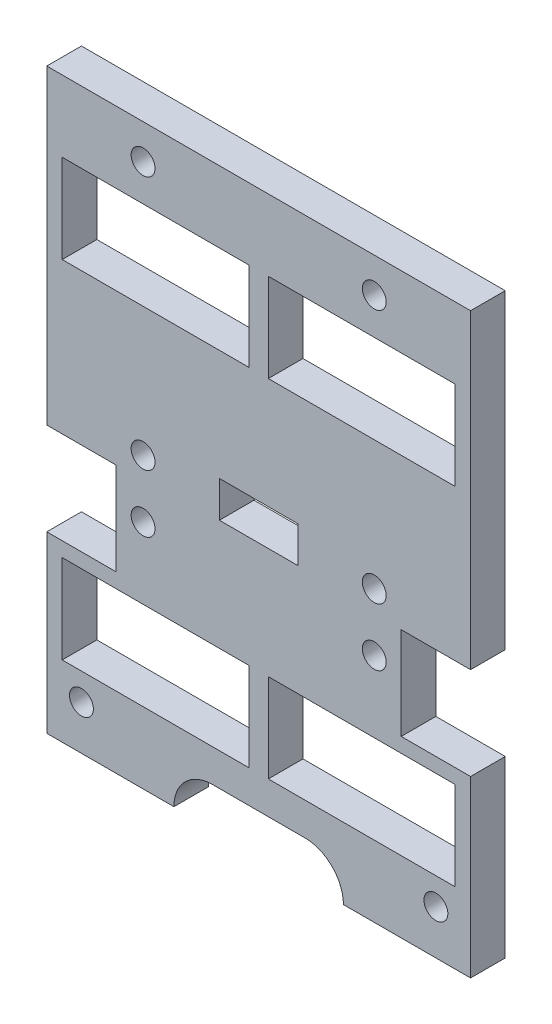
SolidWorks part; units mm, degrees
ref_plane "Front Plane" through (0, 0, 0) normal (0, 0, 1) x (1, 0, 0)
ref_plane "Top Plane" through (0, 0, 0) normal (0, 1, 0) x (1, 0, 0)
ref_plane "Right Plane" through (0, 0, 0) normal (1, 0, 0) x (0, 0, -1)
sketch "Sketch1" plane through (0, 0, 0) normal (0, 0, 1) x (1, 0, 0)
  line L0 (0, -37.5) -> (0, 37.5) construction
  line L1 (-27.5, -37.5) -> (27.5, -37.5)
  line L2 (-27.5, -37.5) -> (-27.5, 37.5)
  line L3 (-27.5, 37.5) -> (27.5, 37.5)
  line L4 (27.5, -37.5) -> (27.5, 37.5)
  line L5 (-27.5, -37.5) -> (27.5, 37.5) construction
  line L6 (-27.5, 37.5) -> (27.5, -37.5) construction
  line L7 (-27.5, 0) -> (27.5, 0) construction
  line L8 (-27.5, 22.5) -> (27.5, 22.5) construction
  line L9 (25.5, 16.75) -> (1.25, 28.25) construction
  line L10 (-25.5, 28.25) -> (-1.25, 28.25)
  line L11 (-25.5, 28.25) -> (-25.5, 16.75)
  line L12 (-25.5, 16.75) -> (-1.25, 16.75)
  line L13 (-1.25, 28.25) -> (-1.25, 16.75)
  line L14 (-25.5, 28.25) -> (-1.25, 16.75) construction
  line L15 (-25.5, 16.75) -> (-1.25, 28.25) construction
  line L16 (25.5, 28.25) -> (1.25, 16.75) construction
  line L17 (1.25, 28.25) -> (1.25, 16.75)
  line L18 (25.5, 16.75) -> (1.25, 16.75)
  line L19 (25.5, 28.25) -> (25.5, 16.75)
  line L20 (25.5, 28.25) -> (1.25, 28.25)
  line L21 (25.5, -28.25) -> (1.25, -16.75) construction
  line L22 (-25.5, -16.75) -> (-1.25, -28.25) construction
  line L23 (-25.5, -28.25) -> (-1.25, -16.75) construction
  line L24 (25.5, -16.75) -> (1.25, -28.25) construction
  line L25 (25.5, -28.25) -> (1.25, -28.25)
  line L26 (25.5, -28.25) -> (25.5, -16.75)
  line L27 (25.5, -16.75) -> (1.25, -16.75)
  line L28 (1.25, -28.25) -> (1.25, -16.75)
  line L29 (-1.25, -28.25) -> (-1.25, -16.75)
  line L30 (-25.5, -16.75) -> (-1.25, -16.75)
  line L31 (-25.5, -28.25) -> (-25.5, -16.75)
  line L32 (-25.5, -28.25) -> (-1.25, -28.25)
  point P0 (0, 0)
  point P12 (-13.375, 22.5)
  point P21 (13.375, 22.5)
  point P30 (13.375, -22.5)
  point P31 (-13.375, -22.5)
  dimension "D1" = 55
  dimension "D2" = 75
  dimension "D3" = 22.5
  dimension "D4" = 24.25
  dimension "D5" = 11.5
  dimension "D6" = 1.25
extrude "Boss-Extrude1" add sketch "Sketch1" along normal blind 4.5
sketch "Sketch2" plane through (0, 0, 4.5) normal (0, 0, 1) x (1, 0, 0)
  line L0 (0, -37.5) -> (0, 37.5) construction
  line L1 (-27.5, -37.5) -> (27.5, -37.5) construction
  line L2 (27.5, 37.5) -> (-27.5, 37.5) construction
  line L3 (-27.5, 0) -> (27.5, 0) construction
  line L4 (-27.5, 37.5) -> (-27.5, -37.5) construction
  line L5 (27.5, -37.5) -> (27.5, 37.5) construction
  line L6 (-15, 0) -> (15, 0) construction
  circle A0 centre (-15, 33) radius 1.55
  circle A1 centre (15, 33) radius 1.55
  circle A2 centre (15, 0) radius 1.55
  circle A3 centre (-15, 0) radius 1.55
  dimension "D1" = 3.1
  dimension "D7" = 3.1
  dimension "D8" = 3.1
  dimension "D2" = 15
  dimension "D3" = 33
  dimension "D4" = 30
  dimension "D5" = 15
  dimension "D6" = 0
extrude "screwHoles" cut sketch "Sketch2" against normal through all
sketch "Sketch3" plane through (0, 0, 4.5) normal (0, 0, 1) x (1, 0, 0)
  line L0 (-27.5, 9) -> (26.0486, 9) construction
  line L1 (-27.5, 37.5) -> (-27.5, -37.5) construction
  line L3 (0, 37.5) -> (0, -37.5) construction
  line L4 (27.5, 37.5) -> (-27.5, 37.5) construction
  line L5 (-27.5, -37.5) -> (27.5, -37.5) construction
  line L6 (19.1, 6.65) -> (8.9, 11.35) construction
  line L7 (-19.1, 11.35) -> (-8.9, 11.35)
  line L8 (-19.1, 11.35) -> (-19.1, 6.65)
  line L9 (-19.1, 6.65) -> (-8.9, 6.65)
  line L10 (-8.9, 11.35) -> (-8.9, 6.65)
  line L11 (-19.1, 11.35) -> (-8.9, 6.65) construction
  line L12 (-19.1, 6.65) -> (-8.9, 11.35) construction
  line L13 (19.1, 11.35) -> (8.9, 6.65) construction
  line L14 (8.9, 11.35) -> (8.9, 6.65)
  line L15 (19.1, 6.65) -> (8.9, 6.65)
  line L16 (19.1, 11.35) -> (19.1, 6.65)
  line L17 (19.1, 11.35) -> (8.9, 11.35)
  line L18 (-27.5, 37.5) -> (-27.5, -37.5) construction
  point P2 (-27.5, 0)
  point P12 (-14, 9)
  point P21 (14, 9)
  dimension "D1" = 10.2
  dimension "D2" = 4.7
  dimension "D3" = 14
  dimension "D4" = 9
extrude "BeltClamp" [suppressed] cut sketch "Sketch3" against normal through all
sketch "Sketch4" plane through (0, 0, 4.5) normal (0, 0, 1) x (1, 0, 0)
  line L0 (-27.5, 0) -> (27.5, 0) construction
  line L1 (-27.5, 37.5) -> (-27.5, -37.5) construction
  line L2 (27.5, -37.5) -> (27.5, 37.5) construction
  line L4 (-5.1, 2.35) -> (5.1, 2.35)
  line L5 (-5.1, 2.35) -> (-5.1, -2.35)
  line L6 (-5.1, -2.35) -> (5.1, -2.35)
  line L7 (5.1, 2.35) -> (5.1, -2.35)
  line L8 (-5.1, 2.35) -> (5.1, -2.35) construction
  line L9 (-5.1, -2.35) -> (5.1, 2.35) construction
  circle A0 centre (-15, 0) radius 1.55 construction
  point P6 (0, 0)
  dimension "D1" = 10.2
  dimension "D2" = 4.7
  dimension "D3" = 0
extrude "mountingPlateTab" cut sketch "Sketch4" against normal through all
sketch "Sketch5" plane through (0, 0, 4.5) normal (0, 0, 1) x (1, 0, 0)
  line L0 (-27.5, -9.75) -> (27.5, -9.75) construction
  line L1 (-27.5, 37.5) -> (-27.5, -37.5) construction
  line L2 (27.5, -37.5) -> (27.5, 37.5) construction
  line L3 (5.1, -2.35) -> (5.1, 2.35) construction
  line L4 (0, -37.5) -> (0, 37.5) construction
  line L5 (-27.5, -37.5) -> (27.5, -37.5) construction
  line L6 (27.5, 37.5) -> (-27.5, 37.5) construction
  line L7 (-20.65, -14.85) -> (-25.35, -4.65) construction
  line L8 (20.65, -4.65) -> (25.35, -4.65)
  line L9 (20.65, -4.65) -> (20.65, -14.85)
  line L10 (20.65, -14.85) -> (25.35, -14.85)
  line L11 (25.35, -4.65) -> (25.35, -14.85)
  line L12 (20.65, -4.65) -> (25.35, -14.85) construction
  line L13 (20.65, -14.85) -> (25.35, -4.65) construction
  line L14 (-20.65, -4.65) -> (-25.35, -14.85) construction
  line L15 (-25.35, -4.65) -> (-25.35, -14.85)
  line L16 (-20.65, -14.85) -> (-25.35, -14.85)
  line L17 (-20.65, -4.65) -> (-20.65, -14.85)
  line L18 (-20.65, -4.65) -> (-25.35, -4.65)
  line L19 (23, -9.75) -> (23, -37.5) construction
  line L20 (-23, -9.75) -> (-23, -37.5) construction
  circle A0 centre (23, -31.75) radius 1.55
  circle A1 centre (-23, -31.75) radius 1.55
  point P6 (5.1, 0)
  point P15 (23, -9.75)
  point P24 (-23, -9.75)
  dimension "D5" = 3.1
  dimension "D1" = 9.75
  dimension "D2" = 10.2
  dimension "D3" = 4.7
  dimension "D4" = 23
  dimension "D6" = 22
extrude "BraceTabs" cut sketch "Sketch5" against normal through all
sketch "Sketch6" plane through (0, 0, 4.5) normal (0, 0, 1) x (1, 0, 0)
  line L0 (-25.35, -9.75) -> (25.35, -9.75) construction
  line L1 (-25.35, -4.65) -> (-25.35, -14.85) construction
  line L2 (25.35, -14.85) -> (25.35, -4.65) construction
  line L3 (0, -2.35) -> (0, -37.5) construction
  line L4 (-5.1, -2.35) -> (5.1, -2.35) construction
  line L5 (-27.5, -37.5) -> (27.5, -37.5) construction
  line L6 (23, -14.85) -> (23, -4.65) construction
  line L7 (20.65, -14.85) -> (25.35, -14.85) construction
  line L8 (25.35, -4.65) -> (20.65, -4.65) construction
  line L9 (20.65, -4.65) -> (20.65, -14.85) construction
  line L10 (19.65, -15.85) -> (26.35, -15.85)
  line L11 (19.65, -15.85) -> (19.65, -3.65)
  line L12 (19.65, -3.65) -> (26.35, -3.65)
  line L13 (26.35, -15.85) -> (26.35, -3.65)
  line L14 (19.65, -15.85) -> (26.35, -3.65) construction
  line L15 (19.65, -3.65) -> (26.35, -15.85) construction
  line L16 (-19.65, -3.65) -> (-26.35, -15.85) construction
  line L17 (-19.65, -15.85) -> (-26.35, -3.65) construction
  line L18 (-23, -14.85) -> (-23, -4.65) construction
  line L19 (-26.35, -15.85) -> (-26.35, -3.65)
  line L20 (-19.65, -3.65) -> (-26.35, -3.65)
  line L21 (-19.65, -15.85) -> (-19.65, -3.65)
  line L22 (-19.65, -15.85) -> (-26.35, -15.85)
  circle A0 centre (23, -9.75) radius 1.55
  circle A1 centre (-23, -9.75) radius 1.55
  point P18 (23, -9.75)
  dimension "D3" = 3.1
  dimension "D1" = 1
  dimension "D2" = 1
extrude "FrontToRear1" [suppressed] add sketch "Sketch6" against normal up to surface (4.5 mm away) up to face at (-24.55, -31.75, 0)
sketch "Sketch7" plane through (0, 0, 4.5) normal (0, 0, 1) x (1, 0, 0)
  line L0 (5.1, 2.35) -> (-5.1, 2.35) construction
  line L1 (-20, -3.35) -> (20, -3.35)
  line L2 (-20, -3.35) -> (-20, 3.35)
  line L3 (-20, 3.35) -> (20, 3.35)
  line L4 (20, -3.35) -> (20, 3.35)
  line L5 (-20, -3.35) -> (20, 3.35) construction
  line L6 (-20, 3.35) -> (20, -3.35) construction
  circle A0 centre (15, 0) radius 1.55 construction
  point P0 (0, 0)
  dimension "D1" = 1
  dimension "D2" = 5
extrude "FrontToRear2" [suppressed] add sketch "Sketch7" against normal through all
sketch "Sketch8" plane through (0, 0, 4.5) normal (0, 0, 1) x (1, 0, 0)
  line L0 (-27.5, -7.5) -> (27.5, -7.5) construction
  line L1 (-27.5, 37.5) -> (-27.5, -37.5) construction
  line L2 (27.5, -37.5) -> (27.5, 37.5) construction
  line L3 (0, -37.5) -> (0, 0) construction
  line L4 (-27.5, -37.5) -> (27.5, -37.5) construction
  circle A0 centre (-15, -7.5) radius 1.55
  circle A1 centre (15, -7.5) radius 1.55
  dimension "D2" = 3.1
  dimension "D1" = 7.5
  dimension "D3" = 15
extrude "ExpansionScrewholes" cut sketch "Sketch8" against normal through all
sketch "Sketch11" plane through (0, 0, 4.5) normal (0, 0, 1) x (1, 0, 0)
  line L0 (13.5615, -8.85) -> (27.5, -8.85) construction
  line L1 (27.5, -37.5) -> (27.5, 37.5) construction
  line L2 (0, 2.35) -> (0, -2.35) construction
  line L3 (36.5, -14.85) -> (18.5, -14.85)
  line L4 (36.5, -14.85) -> (36.5, -2.85)
  line L5 (36.5, -2.85) -> (18.5, -2.85)
  line L6 (18.5, -14.85) -> (18.5, -2.85)
  line L7 (36.5, -14.85) -> (18.5, -2.85) construction
  line L8 (36.5, -2.85) -> (18.5, -14.85) construction
  line L9 (5.1, 2.35) -> (-5.1, 2.35) construction
  line L10 (-5.1, -2.35) -> (5.1, -2.35) construction
  line L11 (-36.5, -2.85) -> (-18.5, -14.85) construction
  line L12 (-36.5, -14.85) -> (-18.5, -2.85) construction
  line L13 (-18.5, -14.85) -> (-18.5, -2.85)
  line L14 (-36.5, -2.85) -> (-18.5, -2.85)
  line L15 (-36.5, -14.85) -> (-36.5, -2.85)
  line L16 (-36.5, -14.85) -> (-18.5, -14.85)
  line L17 (36.5, -2.85) -> (18.5, -14.85) construction
  line L18 (20.65, -14.85) -> (25.35, -14.85) construction
  dimension "D1" = 9
  dimension "D2" = 12
  dimension "D3" = 0
extrude "Cut-Extrude2" cut sketch "Sketch11" against normal through all
sketch "Sketch10" plane through (0, 0, 4.5) normal (0, 0, 1) x (1, 0, 0)
  line L0 (4.7446, 1) -> (27.5, 1) construction
  line L1 (-5.1, 0) -> (5.1, 0) construction
  line L2 (27.5, -37.5) -> (27.5, -14.85) construction
  line L3 (0, 2.35) -> (0, -2.35) construction
  line L4 (36.5, 4) -> (18.5, 4)
  line L5 (36.5, 4) -> (36.5, -2)
  line L6 (36.5, -2) -> (18.5, -2)
  line L7 (18.5, 4) -> (18.5, -2)
  line L8 (36.5, 4) -> (18.5, -2) construction
  line L9 (36.5, -2) -> (18.5, 4) construction
  line L10 (5.1, 2.35) -> (-5.1, 2.35) construction
  line L11 (-5.1, -2.35) -> (5.1, -2.35) construction
  line L12 (-36.5, -2) -> (-18.5, 4) construction
  line L13 (-36.5, 4) -> (-18.5, -2) construction
  line L14 (-4.7446, 1) -> (-27.5, 1) construction
  line L15 (-18.5, 4) -> (-18.5, -2)
  line L16 (-36.5, -2) -> (-18.5, -2)
  line L17 (-36.5, 4) -> (-36.5, -2)
  line L18 (-36.5, 4) -> (-18.5, 4)
  line L19 (36.5, -2) -> (18.5, 4) construction
  line L20 (-5.1, 2.35) -> (-5.1, -2.35) construction
  line L21 (5.1, -2.35) -> (5.1, 2.35) construction
  dimension "D1" = 6
  dimension "D2" = 9
  dimension "D3" = 1
extrude "CableTieSlots" [suppressed] cut sketch "Sketch10" against normal through all
sketch "Sketch9" plane through (0, 0, 4.5) normal (0, 0, 1) x (1, 0, 0)
  line L0 (-6, -37.5) -> (6, -37.5) construction
  line L1 (-27.5, -37.5) -> (27.5, -37.5) construction
  line L2 (-6, -32.5) -> (6, -32.5)
  line L3 (-6, -42.5) -> (6, -42.5)
  arc A0 (-6, -32.5) -> (-6, -42.5) centre (-6, -37.5) ccw
  arc A1 (6, -42.5) -> (6, -32.5) centre (6, -37.5) ccw
  point P4 (0, -37.5)
  dimension "D1" = 12
  dimension "D2" = 5
extrude "RearFanSlot" cut sketch "Sketch9" against normal through all contours L2 A1 L3 A0
equation "\"X-ROD-SPACING\"=45"
equation "\"Y-ROD-SPACING\"=75"
equation "\"Z-ROD-SPACING\"=17.5"
equation "\"Y-BED-OFFSET\"=2"
equation "\"Y-BED-ROD-INSET\"=3.5"
equation "\"Y-BED-SCREW-SPACING\"=209"
equation "\"Y-BED-SCREW-CUTOUT-SLOT-HEIGHT\"=1"
equation "\"T-SLOT-NUT-FILLET-RADIUS\"=0.25"
equation "\"T-SLOT-SCREW-SHAFT-RADIUS\"=1.75"
equation "\"T-SLOT-SCREW-SHAFT-CUTOUT-LENGTH\"=10.5"
equation "\"T-SLOT-NUT-DEPTH\"=4.2"
equation "\"T-SLOT-NUT-WIDTH\"=3"
equation "\"T-SLOT-NUT-END-DISTANCE\"=8"
equation "\"ACRYLIC-THICKNESS\"=10"
equation "\"ACRYLIC-THICKNESS2\"=4.5"
equation "\"ACRYLIC-TAB-CUTOUT-SIZE\"=\"ACRYLIC-THICKNESS\"+\"ACRYLIC-TAB-TOLERANCE\"*2"
equation "\"ACRYLIC-TAB-WIDTH\"=\"ACRYLIC-THICKNESS\""
equation "\"ACRYLIC-M3-HOLE\"=3.1"
equation "\"SMOOTHROD-CAP-SCREW-DISTANCE\"=20"
equation "\"FRAME-WIDTH-INNER\"=370"
equation "\"NEMA17-HOLE-SPACING\"=31"
equation "\"NEMA17-CENTRAL-CUTOUT\"=22.5"
equation "\"Z-BRACKET-REACH\"=55"
equation "\"Z-ROD-INSET\"=16"
equation "\"TOP-BRACKET-SPACING\"=40"
equation "\"SMOOTHROD-X-LENGTH\"=350"
equation "\"SMOOTHROD-Y-LENGTH\"=350"
equation "\"SMOOTHROD-Z-LENGTH\"=350"
equation "\"SMOOTHROD-TIGHTENING-HEADROOM\"=1"
equation "\"LEADSCREW-Z-LENGTH\"=300"
equation "\"SCREW-LENGTH-FRAME\"=\"ACRYLIC-THICKNESS\" + 10"
equation "\"SCREW-LENGTH-MOTOR\"=\"ACRYLIC-THICKNESS\" + 5"
equation "\"SCREW-HEAD-RADIUS\"=6"
equation "\"PRINTED-X-SMOOTHROD-DIAMETER\"=8.2"
equation "\"PRINTED-X-SMOOTHROD-CUTOUT\"=10"
equation "\"PRINTED-X-BASE-HEIGHT\"=10"
equation "\"PRINTED-LM8UU-CUTOUT-SIZE\"=15.25"
equation "\"PRINTED-LM8UU-CUTOUT-LENGTH\"=24.5"
equation "\"PRINTED-X-IDLER-HEIGHT\"=16"
equation "\"PSU-MOUNTING-WIDTH\"=95"
equation "\"PSU-MOUNTING-HEIGHT\"=177"
equation "\"Y-BELT-TO-ROD-DISTANCE\"=20"
equation "\"SPOOL-HOLDER-ROD-SPACING\"=150"
equation "\"D3@Sketch1\"=\"X-ROD-SPACING\"/2"
equation "\"D4@Sketch1\"=\"ACRYLIC-X-CARRIAGE-LM8UU-CUTOUT-WIDTH\""
equation "\"D1@Boss-Extrude1\"=\"ACRYLIC-THICKNESS2\""
equation "\"D1@Sketch2\"=\"ACRYLIC-M3-HOLE\""
equation "\"D1@Sketch3\"=\"ACRYLIC-TAB-CUTOUT-SIZE\""
equation "\"D2@Sketch3\"=\"ACRYLIC-THICKNESS2\"+\"ACRYLIC-TAB-TOLERANCE\"*2"
equation "\"ACRYLIC-X-CARRIAGE-WIDTH\"=55"
equation "\"ACRYLIC-X-CARRIAGE-HEIGHT\"=75"
equation "\"D1@Sketch1\"=\"ACRYLIC-X-CARRIAGE-WIDTH\""
equation "\"D2@Sketch1\"=\"ACRYLIC-X-CARRIAGE-HEIGHT\""
equation "\"ACRYLIC-X-CARRIAGE-CENTER-TAB-SPACING\"=14"
equation "\"D3@Sketch3\"=\"ACRYLIC-X-CARRIAGE-CENTER-TAB-SPACING\""
equation "\"SCREW-LENGTH-EXTRUDER\"=28"
equation "\"ACRYLIC-X-CARRIAGE-SCREW-SPACING-X\"=15"
equation "\"ACRYLIC-X-CARRIAGE-SCREW-SPACING-Y\"=33"
equation "\"D2@Sketch2\"=\"ACRYLIC-X-CARRIAGE-SCREW-SPACING-X\""
equation "\"D3@Sketch2\"=\"ACRYLIC-X-CARRIAGE-SCREW-SPACING-Y\""
equation "\"D1@Sketch4\"=\"ACRYLIC-TAB-CUTOUT-SIZE\""
equation "\"D2@Sketch4\"=\"ACRYLIC-THICKNESS2\"+\"ACRYLIC-TAB-TOLERANCE\"*2"
equation "\"D2@Sketch5\"=\"ACRYLIC-TAB-CUTOUT-SIZE\""
equation "\"D3@Sketch5\"=\"ACRYLIC-THICKNESS2\"+\"ACRYLIC-TAB-TOLERANCE\"*2"
equation "\"ACRYLIC-X-CARRIAGE-EXTRUDER-SHELF-DEPTH\"=\"ACRYLIC-X-CARRIAGE-EXTRUDER-OFFSET\" + 30"
equation "\"ACRYLIC-X-CARRIAGE-EXTRUDER-BRACE-SPACING\"=23"
equation "\"D4@Sketch5\"=\"ACRYLIC-X-CARRIAGE-EXTRUDER-BRACE-SPACING\""
equation "\"D1@Sketch5\"=\"ACRYLIC-THICKNESS2\"/2 + 7.5"
equation "\"D4@Sketch2\"=\"ACRYLIC-X-CARRIAGE-SCREW-SPACING-X\"*2"
equation "\"D5@Sketch2\"=\"ACRYLIC-X-CARRIAGE-SCREW-SPACING-X\""
equation "\"D7@Sketch2\"=\"ACRYLIC-M3-HOLE\""
equation "\"D8@Sketch2\"=\"ACRYLIC-M3-HOLE\""
equation "\"ACRYLIC-X-CARRIAGE-LM8UU-CUTOUT-WIDTH\"=24.25"
equation "\"ACRYLIC-TAB-TOLERANCE\"=.1"
equation "\"ACRYLIC-X-CARRIAGE-EXTRUDER-OFFSET\"=26"
equation "\"ACRYLIC-X-CARRIAGE-EXTRUDER-ANGLE\"=90"
equation "\"ACRYLIC-X-CARRIAGE-EXTRUDER-BRACE-TAB-OFFSET\"=20"
equation "\"ACRYLIC-X-CARRIAGE-EXTRUDER-BRACE-HEIGHT\"=35"
equation "\"ACRYLIC-X-CARRIAGE-EXTRUDER-BRACE-SCREW-SPACING\"=22"
equation "\"D5@Sketch5\"=\"ACRYLIC-M3-HOLE\""
equation "\"D3@Sketch6\"=\"ACRYLIC-M3-HOLE\""
equation "\"ACRYLIC-X-CARRIAGE-LM8UU-CUTOUT-HEIGHT\"=11.5"
equation "\"ACRYLIC-X-CARRIAGE-DUAL-WIDTH-MULTIPLIER\"=1.65"
equation "\"ACRYLIC-X-CARRIAGE-DUAL-HOTEND-SPACING\"=42"
equation "\"ACRYLIC-X-CARRIAGE-DUAL-WIDTH\"=103"
equation "\"ACRYLIC-X-CARRIAGE-DUAL-HOTEND-SEPARATION\"=35"
equation "\"ACRYLIC-X-CARRIAGE-DUAL-MOUNT-PLATE-DEPTH\"=76"
equation "\"ACRYLIC-X-CARRIAGE-DUAL-MOUNT-BRACE-WIDTH\"=45"
equation "\"ACRYLIC-X-CARRIAGE-DUAL-MOUNT-SCREW-WIDTH\"=40"
equation "\"D5@Sketch1\"=\"ACRYLIC-X-CARRIAGE-LM8UU-CUTOUT-HEIGHT\""
equation "\"D2@Sketch8\"=\"ACRYLIC-M3-HOLE\""
